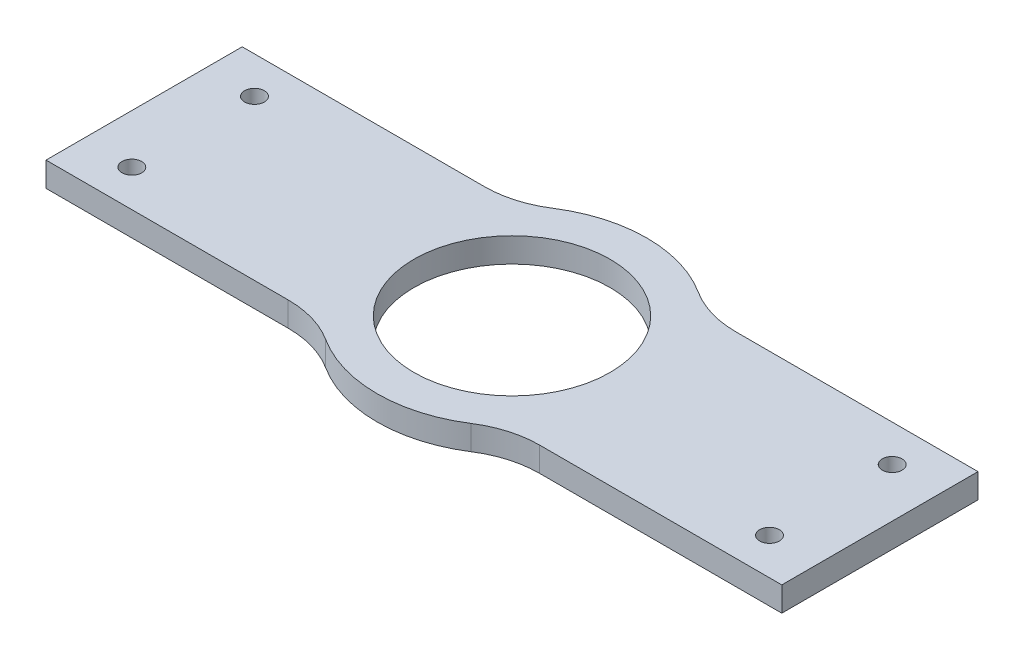
SolidWorks part; units mm, degrees
material "6061-T6 (SS)"
ref_plane "Front" through (0, 0, 0) normal (0, 0, 1) x (1, 0, 0)
ref_plane "Top" through (0, 0, 0) normal (0, 1, 0) x (1, 0, 0)
ref_plane "Right" through (0, 0, 0) normal (1, 0, 0) x (0, 0, -1)
sketch "Sketch1" plane through (0, 0, 0) normal (0, 1, 0) x (1, 0, 0)
  line L0 (190.5, 0) -> (190.5, 19.05) construction
  line L1 (0, 0) -> (62.7159, 0)
  line L2 (0, 0) -> (0, 50.8)
  line L3 (0, 50.8) -> (62.7159, 50.8)
  line L4 (190.5, 0) -> (190.5, 50.8)
  line L5 (0, 50.8) -> (190.5, 0) construction
  line L6 (127.7841, 50.8) -> (190.5, 50.8)
  line L7 (127.7841, 0) -> (190.5, 0)
  arc A0 (76.4145, -4.0105) -> (114.0855, -4.0105) centre (95.25, 25.4) ccw
  arc A1 (114.0855, 54.8105) -> (76.4145, 54.8105) centre (95.25, 25.4) ccw
  arc A2 (62.7159, 0) -> (76.4145, -4.0105) centre (62.7159, -25.4) cw
  arc A3 (127.7841, 0) -> (114.0855, -4.0105) centre (127.7841, -25.4) ccw
  arc A4 (127.7841, 50.8) -> (114.0855, 54.8105) centre (127.7841, 76.2) cw
  arc A5 (62.7159, 50.8) -> (76.4145, 54.8105) centre (62.7159, 76.2) ccw
  point P18 (119.2207, 50.8)
  dimension "D2" = 69.85
  dimension "D3" = 25.4
  dimension "D1" = 50.8
extrude "Boss-Extrude1" add sketch "Sketch1" along normal blind 6.35
sketch "Sketch4" plane through (0, 6.35, 0) normal (0, 1, 0) x (1, 0, 0)
  line L0 (0, 0) -> (12.7, 9.525) construction
  line L1 (0, 0) -> (62.7159, 0) construction
  line L6 (12.7, 9.525) -> (12.7, 41.275) construction
  line L7 (12.7, 41.275) -> (25.4, 50.8) construction
  line L8 (62.7159, 50.8) -> (0, 50.8) construction
  line L9 (95.25, 0) -> (95.25, 25.4) construction
  arc A0 (76.4145, -4.0105) -> (114.0855, -4.0105) centre (95.25, 25.4) ccw construction
  point P0 (12.7, 41.275)
  point P4 (12.7, 9.525)
  point P34 (177.8, 9.525)
  point P36 (177.8, 41.275)
  dimension "D1" = 31.75
  dimension "D2" = 25.4
hole_wizard "#10 Clearance Hole1" positions "Sketch4" profile "Sketch3" hole size "#10" standard "ANSI Inch" end condition up to next
sketch "Sketch3" plane through (12.7, 6.35, -41.275) normal (1, 0, 0) x (0, 0, 1)
  line L0 (0, 0) -> (0, 6.35)
  line L1 (0, 6.35) -> (2.5527, 6.35)
  line L2 (2.5527, 6.35) -> (2.5527, 0)
  line L5 (2.5527, 0) -> (0, 0)
  line L11 (0, -6.35) -> (0, 107.95) construction
  dimension "Thru Hole Dia." = 5.1054
  dimension "Thru Hole Depth" = 6.35
sketch "Sketch5" plane through (0, 6.35, 0) normal (0, 1, 0) x (1, 0, 0)
  circle A0 centre (95.25, 25.4) radius 25.4
  arc A1 (114.0855, 54.8105) -> (76.4145, 54.8105) centre (95.25, 25.4) ccw construction
  dimension "D1" = 50.8
extrude "Cut-Extrude1" cut sketch "Sketch5" against normal through all
